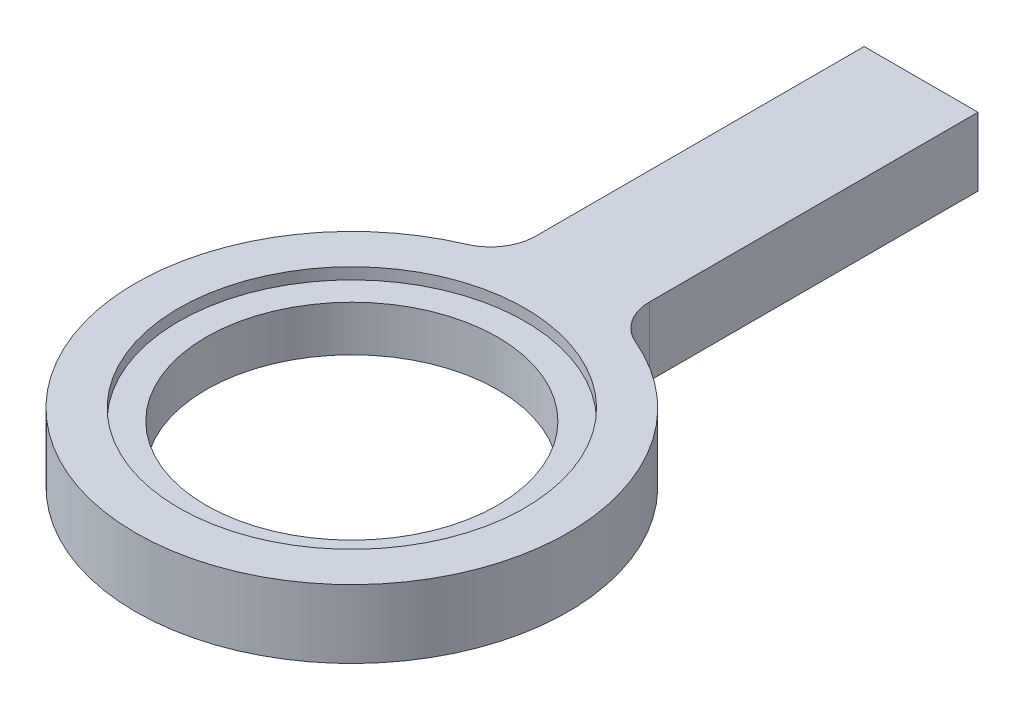
SolidWorks part; units mm, degrees
ref_plane "前视基准面" through (0, 0, 0) normal (0, 0, 1) x (1, 0, 0)
ref_plane "上视基准面" through (0, 0, 0) normal (0, 1, 0) x (1, 0, 0)
ref_plane "右视基准面" through (0, 0, 0) normal (1, 0, 0) x (0, 0, -1)
other "Configuration Table"
sketch "草图1" plane through (0, 0, 0) normal (0, 1, 0) x (1, 0, 0)
  circle A0 centre (0, 0) radius 9.5
  circle A1 centre (0, 0) radius 6.4
  dimension "D1" = 19
  dimension "D2" = 12.8
extrude "凸台-拉伸1" add sketch "草图1" along normal blind 2 contours A0 | A1
sketch "草图2" plane through (0, 2, 0) normal (0, 1, 0) x (1, 0, 0)
  circle A0 centre (0, 0) radius 7.6
  circle A1 centre (0, 0) radius 9.5
  circle A2 centre (0, 0) radius 9.5 construction
  dimension "D1" = 15.2
extrude "凸台-拉伸2" add sketch "草图2" along normal blind 0.5
extrude "凸台-拉伸3" add sketch "草图2<2>" against normal blind 0.5 from surface starting at face at (0, 0, 9.5)
sketch "草图2<2>" plane through (0, 2, 0) normal (0, 1, 0) x (1, 0, 0) same geometry as "草图2"
sketch "草图4" plane through (0, 2.5, 0) normal (0, 1, 0) x (1, 0, 0)
  line L1 (-2.5, 0) -> (2.5, 0)
  line L2 (-2.5, 0) -> (-2.5, 25)
  line L3 (-2.5, 25) -> (2.5, 25)
  line L4 (2.5, 0) -> (2.5, 25)
  circle A0 centre (0, 0) radius 9.5
  circle A1 centre (0, 0) radius 9.5 construction
  circle M4 centre (0, 0) radius 9.5
  dimension "D1" = 25
  dimension "D2" = 5
extrude "凸台-拉伸4" add sketch "草图4" against normal up to surface (3 mm away) contours L4 L3 L2 M4 region at (0, 2.5, -17.1943) up to face at (0, -0.5, 7.6)
fillet "圆角1" radius 2 2 edges at (-2.5, 1, -9.1652) (2.5, 1, -9.1652)
